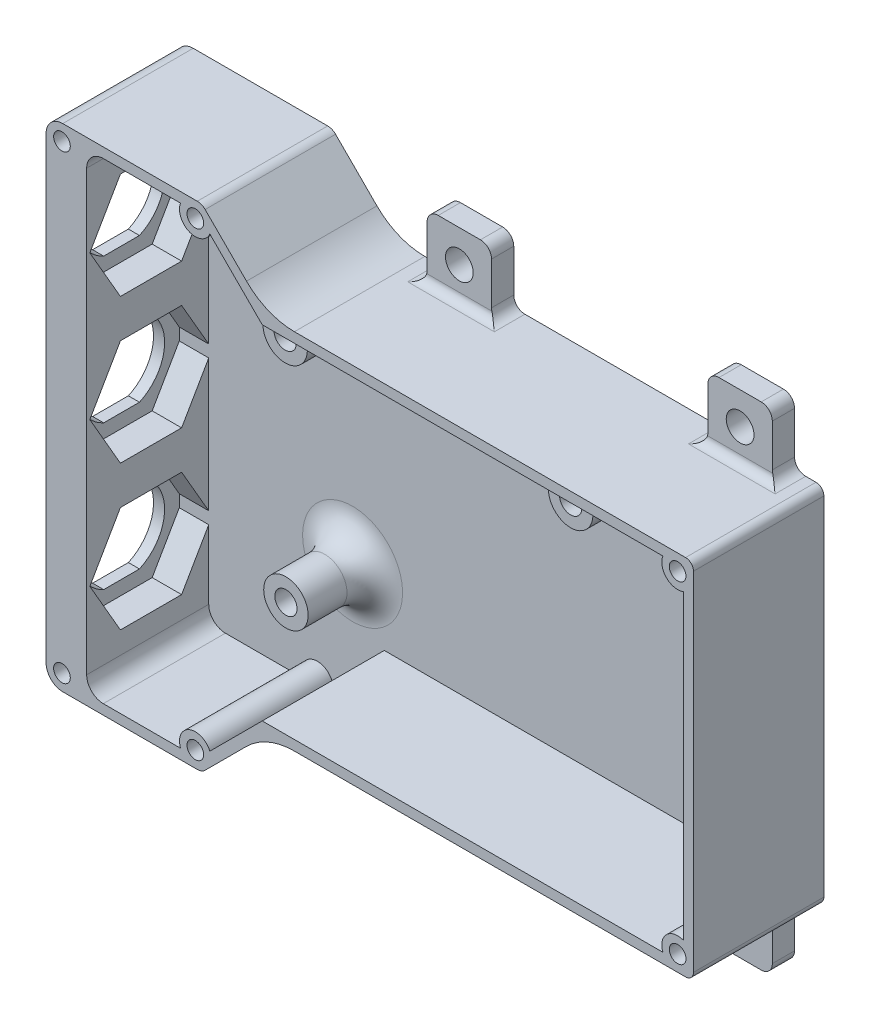
SolidWorks part; units mm, degrees
ref_plane "Front Plane" through (0, 0, 0) normal (0, 0, 1) x (1, 0, 0)
ref_plane "Top Plane" through (0, 0, 0) normal (0, 1, 0) x (1, 0, 0)
ref_plane "Right Plane" through (0, 0, 0) normal (1, 0, 0) x (0, 0, -1)
sketch "Sketch1" plane through (0, 0, 0) normal (0, 0, 1) x (1, 0, 0)
  line L0 (21.6569, -104.2696) -> (33.2669, -92.6596)
  line L1 (21.6569, -11.2696) -> (33.2619, -22.8746)
  line L2 (22.8284, -103.098) -> (34.4384, -91.488) construction
  line L3 (22.8284, -12.4412) -> (34.4334, -24.0462) construction
  line L10 (0, -100.2696) -> (20, -100.2696)
  line L11 (0, -15.2696) -> (20, -15.2696)
  line L12 (20, -100.2696) -> (31.61, -88.6596)
  line L13 (96.455, -88.6596) -> (8, -88.6596) construction
  line L14 (8, -26.8746) -> (96.455, -26.8746) construction
  line L15 (20, -15.2696) -> (31.605, -26.8746)
  line L16 (1.6569, -104.2696) -> (21.6569, -104.2696)
  line L17 (1.6569, -11.2696) -> (21.6569, -11.2696)
  line L24 (96.455, -88.6596) -> (31.61, -88.6596)
  line L26 (31.605, -26.8746) -> (96.455, -26.8746)
  line L27 (96.455, -26.8746) -> (96.455, -88.6596)
  line L28 (100.455, -92.6596) -> (33.2669, -92.6596)
  line L29 (33.2619, -22.8746) -> (100.455, -22.8746)
  line L31 (100.455, -22.8746) -> (100.455, -92.6596)
  line L33 (0, -100.2696) -> (-18.3, -100.2696)
  line L35 (0, -15.2696) -> (-18.3, -15.2696)
  line L36 (-18.3, -15.2696) -> (-18.3, -11.2696)
  line L37 (-18.3, -11.2696) -> (1.6569, -11.2696)
  line L38 (-18.3, -100.2696) -> (-18.3, -104.2696)
  line L39 (-18.3, -104.2696) -> (1.6569, -104.2696)
  line L45 (100.455, -92.6596) -> (4, -92.6596) construction
  line L46 (4, -92.6596) -> (4, -22.8746) construction
  line L47 (4, -22.8746) -> (100.455, -22.8746) construction
  line L52 (8, -88.6596) -> (8, -26.8746) construction
  dimension "D1" = 4
  dimension "D3" = 4
  dimension "D2" = 4
extrude "Boss-Extrude1" add sketch "Sketch1" along normal blind 36.78
sketch "Sketch2" plane through (0, 0, 0) normal (0, 0, -1) x (-1, 0, 0)
  line L0 (18.3, -15.2696) -> (18.3, -100.2696)
  line L16 (-33.2669, -92.6596) -> (-21.6569, -104.2696)
  line L17 (-31.61, -88.6596) -> (-96.455, -88.6596)
  line L18 (-96.455, -88.6596) -> (-96.455, -26.8746)
  line L19 (-96.455, -26.8746) -> (-31.605, -26.8746)
  line L20 (-33.2669, -92.6596) -> (-21.6569, -104.2696)
  line L21 (-20, -15.2696) -> (18.3, -15.2696)
  line L22 (18.3, -15.2696) -> (18.3, -11.2696)
  line L23 (18.3, -11.2696) -> (-21.6569, -11.2696)
  line L24 (-20, -100.2696) -> (-31.61, -88.6596)
  line L25 (-33.2619, -22.8746) -> (-100.455, -22.8746)
  line L26 (-100.455, -22.8746) -> (-100.455, -92.6596)
  line L27 (-100.455, -92.6596) -> (-33.2669, -92.6596)
  line L29 (-21.6569, -104.2696) -> (18.3, -104.2696)
  line L30 (18.3, -104.2696) -> (18.3, -100.2696)
  line L31 (18.3, -100.2696) -> (-20, -100.2696)
  line L33 (-31.605, -26.8746) -> (-20, -15.2696)
  line L35 (-21.6569, -11.2696) -> (-33.2619, -22.8746)
  line L36 (-21.6569, -11.2696) -> (-33.2619, -22.8746)
  line L38 (18.3, -15.2696) -> (18.3, -11.2696)
  line L39 (18.3, -11.2696) -> (-21.6569, -11.2696)
  line L41 (-33.2619, -22.8746) -> (-100.455, -22.8746)
  line L42 (-100.455, -22.8746) -> (-100.455, -92.6596)
  line L43 (-100.455, -92.6596) -> (-33.2669, -92.6596)
  line L45 (-21.6569, -104.2696) -> (18.3, -104.2696)
  line L46 (18.3, -104.2696) -> (18.3, -100.2696)
  dimension "D1" = 0
extrude "Boss-Extrude2" add sketch "Sketch2" against normal blind 3.5
sketch "Sketch4" plane through (-5.3, 0, 0) normal (1, 0, 0) x (0, 0, -1)
  line L0 (-13.8923, -90.5196) -> (-10.7395, -90.5196) construction
  line L1 (-13.8923, -90.5196) -> (-17.0451, -90.5196) construction
  line L2 (-13.8923, -77.0196) -> (-10.7395, -77.0196) construction
  line L3 (-13.8923, -77.0196) -> (-17.0451, -77.0196) construction
  line L4 (-13.8923, -64.5196) -> (-10.7395, -64.5196) construction
  line L5 (-13.8923, -64.5196) -> (-17.0451, -64.5196) construction
  line L6 (-13.8923, -51.0196) -> (-10.7395, -51.0196) construction
  line L7 (-13.8923, -51.0196) -> (-17.0451, -51.0196) construction
  line L8 (-13.8923, -38.5196) -> (-17.0451, -38.5196) construction
  line L9 (-13.8923, -38.5196) -> (-10.7395, -38.5196) construction
  line L10 (-13.8923, -25.0196) -> (-10.7395, -25.0196) construction
  line L11 (-13.8923, -25.0196) -> (-17.0451, -25.0196) construction
  line L12 (-13.8923, -90.5196) -> (-10.7395, -90.5196)
  line L13 (-13.8923, -90.5196) -> (-17.0451, -90.5196)
  line L14 (-13.8923, -77.0196) -> (-10.7395, -77.0196)
  line L15 (-13.8923, -77.0196) -> (-17.0451, -77.0196)
  line L16 (-13.8923, -64.5196) -> (-10.7395, -64.5196)
  line L17 (-13.8923, -64.5196) -> (-17.0451, -64.5196)
  line L18 (-13.8923, -51.0196) -> (-10.7395, -51.0196)
  line L19 (-13.8923, -51.0196) -> (-17.0451, -51.0196)
  line L20 (-13.8923, -38.5196) -> (-17.0451, -38.5196)
  line L21 (-13.8923, -38.5196) -> (-10.7395, -38.5196)
  line L22 (-13.8923, -25.0196) -> (-10.7395, -25.0196)
  line L23 (-13.8923, -25.0196) -> (-17.0451, -25.0196)
  line L24 (-13.8923, -38.8196) -> (-17.111, -38.8196)
  line L25 (-13.8923, -38.8196) -> (-10.6736, -38.8196)
  line L26 (-13.8923, -24.7196) -> (-10.6736, -24.7196)
  line L27 (-13.8923, -24.7196) -> (-17.111, -24.7196)
  line L28 (-13.8923, -64.8196) -> (-17.111, -64.8196)
  line L29 (-13.8923, -64.8196) -> (-10.6736, -64.8196)
  line L30 (-13.8923, -50.7196) -> (-10.6736, -50.7196)
  line L31 (-13.8923, -50.7196) -> (-17.111, -50.7196)
  line L32 (-13.8923, -90.8196) -> (-17.111, -90.8196)
  line L33 (-13.8923, -90.8196) -> (-10.6736, -90.8196)
  line L34 (-13.8923, -76.7196) -> (-10.6736, -76.7196)
  line L35 (-13.8923, -76.7196) -> (-17.111, -76.7196)
  line L36 (-36.78, -100.2696) -> (-3.5, -100.2696)
  line L37 (-36.78, -100.2696) -> (-3.5, -100.2696)
  line L38 (-3.5, -100.2696) -> (-3.5, -15.2696)
  line L39 (-3.5, -100.2696) -> (-3.5, -15.2696)
  line L40 (-3.5, -15.2696) -> (-36.78, -15.2696)
  line L41 (-3.5, -15.2696) -> (-36.78, -15.2696)
  line L42 (-36.78, -15.2696) -> (-36.78, -100.2696)
  arc A0 (-17.0451, -77.0196) -> (-17.0451, -90.5196) centre (-13.8923, -83.7696) ccw construction
  arc A1 (-10.7395, -90.5196) -> (-10.7395, -77.0196) centre (-13.8923, -83.7696) ccw construction
  arc A2 (-10.7395, -64.5196) -> (-10.7395, -51.0196) centre (-13.8923, -57.7696) ccw construction
  arc A3 (-17.0451, -51.0196) -> (-17.0451, -64.5196) centre (-13.8923, -57.7696) ccw construction
  arc A4 (-17.0451, -25.0196) -> (-17.0451, -38.5196) centre (-13.8923, -31.7696) ccw construction
  arc A5 (-10.7395, -38.5196) -> (-10.7395, -25.0196) centre (-13.8923, -31.7696) ccw construction
  arc A6 (-17.0451, -77.0196) -> (-17.0451, -90.5196) centre (-13.8923, -83.7696) ccw
  arc A7 (-10.7395, -90.5196) -> (-10.7395, -77.0196) centre (-13.8923, -83.7696) ccw
  arc A8 (-10.7395, -64.5196) -> (-10.7395, -51.0196) centre (-13.8923, -57.7696) ccw
  arc A9 (-17.0451, -51.0196) -> (-17.0451, -64.5196) centre (-13.8923, -57.7696) ccw
  arc A10 (-17.0451, -25.0196) -> (-17.0451, -38.5196) centre (-13.8923, -31.7696) ccw
  arc A11 (-10.7395, -38.5196) -> (-10.7395, -25.0196) centre (-13.8923, -31.7696) ccw
  arc A12 (-17.111, -24.7196) -> (-17.111, -38.8196) centre (-13.8923, -31.7696) ccw
  arc A13 (-10.6736, -38.8196) -> (-10.6736, -24.7196) centre (-13.8923, -31.7696) ccw
  arc A14 (-17.111, -50.7196) -> (-17.111, -64.8196) centre (-13.8923, -57.7696) ccw
  arc A15 (-10.6736, -64.8196) -> (-10.6736, -50.7196) centre (-13.8923, -57.7696) ccw
  arc A16 (-17.111, -76.7196) -> (-17.111, -90.8196) centre (-13.8923, -83.7696) ccw
  arc A17 (-10.6736, -90.8196) -> (-10.6736, -76.7196) centre (-13.8923, -83.7696) ccw
  line M1 (-21.5451, -64.5196) -> (-18.3923, -64.5196)
  arc M2 (-18.3923, -64.5196) -> (-18.3923, -51.0196) centre (-18.3923, -57.7696) cw
  line M3 (-18.3923, -51.0196) -> (-21.5451, -51.0196)
  arc M4 (-21.5451, -51.0196) -> (-21.5451, -64.5196) centre (-18.3923, -57.7696) ccw
  dimension "D1" = 0.3
extrude "Boss-Extrude3" add sketch "Sketch4" against normal blind 2 contours L41 L42 L37 L39 A17 L33 L32 A16 L35 L34 A15 L29 L28 A14 L31 L30 A13 L25 L24 A12 L27 L26 M1 M4 M3 M2 | M4 M1 M2 M3 region at (-5.3, -57.7696, 35.8672) region at (-5.3, -57.7696, 25.6881)
sketch "Sketch5" plane through (-5.3, 0, 0) normal (1, 0, 0) x (0, 0, -1)
  line L18 (-13.8923, -24.7196) -> (-13.8923, -38.8196)
  line L19 (-10.6736, -24.7196) -> (-17.111, -24.7196) construction
  line L20 (-17.111, -38.8196) -> (-10.6736, -38.8196) construction
  line L21 (-13.8923, -50.7196) -> (-13.8923, -64.8196)
  line L22 (-10.6736, -50.7196) -> (-17.111, -50.7196) construction
  line L23 (-17.111, -64.8196) -> (-10.6736, -64.8196) construction
  line L24 (-13.8923, -76.7196) -> (-13.8923, -90.8196)
  line L25 (-10.6736, -76.7196) -> (-17.111, -76.7196) construction
  line L26 (-17.111, -90.8196) -> (-10.6736, -90.8196) construction
  line L27 (-24.9116, -83.7696) -> (-19.402, -93.3126)
  line L28 (-24.7384, -31.7696) -> (-19.3154, -41.1626)
  line L29 (-19.3154, -41.1626) -> (-8.4692, -41.1626)
  line L30 (-8.4692, -41.1626) -> (-3.0462, -31.7696)
  line L31 (-3.0462, -31.7696) -> (-8.4692, -22.3766)
  line L32 (-8.4692, -22.3766) -> (-19.3154, -22.3766)
  line L33 (-19.3154, -22.3766) -> (-24.7384, -31.7696)
  line L34 (-24.7384, -57.7696) -> (-19.3154, -67.1626)
  line L35 (-19.3154, -67.1626) -> (-8.4692, -67.1626)
  line L36 (-36.78, -100.2696) -> (-3.5, -100.2696) construction
  line L37 (-36.78, -15.2696) -> (-36.78, -100.2696) construction
  line L38 (-3.5, -15.2696) -> (-36.78, -15.2696) construction
  line L39 (-3.5, -100.2696) -> (-3.5, -15.2696) construction
  line L40 (-36.78, -100.2696) -> (-3.5, -100.2696)
  line L41 (-36.78, -15.2696) -> (-36.78, -100.2696)
  line L42 (-3.5, -15.2696) -> (-36.78, -15.2696)
  line L43 (-3.5, -100.2696) -> (-3.5, -15.2696)
  line L44 (-8.4692, -67.1626) -> (-3.0462, -57.7696)
  line L45 (-3.0462, -57.7696) -> (-8.4692, -48.3766)
  line L46 (-8.4692, -48.3766) -> (-19.3154, -48.3766)
  line L47 (-19.3154, -48.3766) -> (-24.7384, -57.7696)
  line L48 (-24.7384, -83.7696) -> (-19.3154, -93.1626)
  line L49 (-19.3154, -93.1626) -> (-8.4692, -93.1626)
  line L50 (-8.4692, -93.1626) -> (-3.0462, -83.7696)
  line L51 (-3.0462, -83.7696) -> (-8.4692, -74.3766)
  line L52 (-8.4692, -74.3766) -> (-19.3154, -74.3766)
  line L53 (-19.3154, -74.3766) -> (-24.7384, -83.7696)
  line L54 (-19.402, -93.3126) -> (-8.3826, -93.3126)
  line L55 (-8.3826, -93.3126) -> (-2.873, -83.7696)
  line L56 (-2.873, -83.7696) -> (-8.3826, -74.2266)
  line L57 (-8.3826, -74.2266) -> (-19.402, -74.2266)
  line L58 (-19.402, -74.2266) -> (-24.9116, -83.7696)
  line L59 (-19.402, -22.2266) -> (-24.9116, -31.7696)
  line L60 (-24.9116, -31.7696) -> (-19.402, -41.3126)
  line L61 (-19.402, -41.3126) -> (-8.3826, -41.3126)
  line L62 (-8.3826, -41.3126) -> (-2.873, -31.7696)
  line L63 (-2.873, -31.7696) -> (-8.3826, -22.2266)
  line L64 (-8.3826, -22.2266) -> (-19.402, -22.2266)
  line L65 (-19.402, -48.2266) -> (-24.9116, -57.7696)
  line L66 (-24.9116, -57.7696) -> (-19.402, -67.3126)
  line L67 (-19.402, -67.3126) -> (-8.3826, -67.3126)
  line L68 (-8.3826, -67.3126) -> (-2.873, -57.7696)
  line L69 (-2.873, -57.7696) -> (-8.3826, -48.2266)
  line L70 (-8.3826, -48.2266) -> (-19.402, -48.2266)
  circle A0 centre (-13.8923, -31.7696) radius 9.393 construction
  circle A1 centre (-13.8923, -57.7696) radius 9.393 construction
  circle A2 centre (-13.8923, -83.7696) radius 9.393 construction
  line M16 (-3.5, -15.2696) -> (-36.78, -15.2696)
  line M17 (-36.78, -15.2696) -> (-36.78, -100.2696)
  line M18 (-36.78, -100.2696) -> (-3.5, -100.2696)
  line M19 (-3.5, -100.2696) -> (-3.5, -15.2696)
  dimension "D1" = 0.15
extrude "Boss-Extrude4" add sketch "Sketch5" along normal up to surface (5.3 mm away) contours L46 L45 L44 L34 L32 L30 L29 L28 M19 M16 M17 M18 region at (-5.3, -88.9975, 22.9473)
sketch "Sketch6" plane through (0, 0, 36.78) normal (0, 0, 1) x (1, 0, 0)
  line L1 (-48.9743, 0) -> (133.8378, 0)
  line L2 (-48.9743, 0) -> (-48.9743, -122.4446)
  line L3 (-48.9743, -122.4446) -> (133.8378, -122.4446)
  line L4 (133.8378, 0) -> (133.8378, -122.4446)
extrude "Cut-Extrude1" cut sketch "Sketch6" against normal blind 4
ref_plane "Plane1" through (5, 0, 0) normal (1, 0, 0) x (0, 0, -1)
fillet "Fillet4" radius 10 2 edges at (33.2669, -92.6596, 16.39) (33.2619, -22.8746, 16.39)
sketch "Sketch8" plane through (0, 0, 32.78) normal (0, 0, 1) x (1, 0, 0)
  line L0 (100.455, -92.6596) -> (100.455, -22.8746) construction
  line L3 (100.455, -88.6596) -> (100.455, -26.8746)
  line L6 (96.455, -26.8746) -> (96.455, -88.6596)
  line L7 (96.455, -26.8746) -> (100.455, -26.8746)
  line L8 (96.455, -88.6596) -> (100.455, -88.6596)
extrude "Cut-Extrude2" cut sketch "Sketch8" against normal up to surface (29.28 mm away) up to face at (13.2163, -57.7691, 3.5)
sketch "Sketch9" plane through (100.455, 0, 0) normal (1, 0, 0) x (0, 0, -1)
  line L0 (-32.78, -92.6596) -> (-32.78, -88.6596) construction
  line L1 (-3.5, -88.6596) -> (-32.78, -88.6596) construction
  line L2 (-32.78, -92.6596) -> (0, -92.6596) construction
  line L3 (0, -92.6596) -> (0, -22.8746) construction
  line L4 (-3.5, -88.6596) -> (-3.5, -26.8746) construction
  line L5 (-3.5, -26.8746) -> (-32.78, -26.8746) construction
  line L6 (-32.78, -26.8746) -> (-32.78, -22.8746) construction
  line L7 (-32.78, -22.8746) -> (0, -22.8746) construction
  line L8 (-32.78, -92.6596) -> (-32.78, -88.6596)
  line L9 (-3.5, -88.6596) -> (-32.78, -88.6596)
  line L10 (-32.78, -92.6596) -> (0, -92.6596)
  line L11 (0, -92.6596) -> (0, -22.8746)
  line L12 (-3.5, -88.6596) -> (-3.5, -26.8746)
  line L13 (-3.5, -26.8746) -> (-32.78, -26.8746)
  line L14 (-32.78, -26.8746) -> (-32.78, -22.8746)
  line L15 (-32.78, -22.8746) -> (0, -22.8746)
extrude "Boss-Extrude6" add sketch "Sketch9" along normal blind 11
sketch "Sketch10" plane through (0, 0, 32.78) normal (0, 0, 1) x (1, 0, 0)
  line L0 (111.455, -88.6596) -> (31.61, -88.6596) construction
  line L2 (31.605, -26.8746) -> (111.455, -26.8746) construction
  line L4 (111.455, -88.6596) -> (107.455, -88.6596)
  line L6 (107.455, -26.8746) -> (111.455, -26.8746)
  line L8 (111.455, -26.8746) -> (107.455, -26.8746)
  line L9 (107.455, -26.8746) -> (107.455, -88.6596)
  line L10 (111.455, -26.8746) -> (111.455, -88.6596)
  line M1 (31.605, -26.8746) -> (111.455, -26.8746)
  line M19 (111.455, -88.6596) -> (31.61, -88.6596)
extrude "Boss-Extrude7" add sketch "Sketch10" against normal up to surface (29.28 mm away) contours L10 L9 M1 M19 region at (109.455, -57.7671, 32.78) up to face at (-12.8, -57.7696, 3.5)
sketch "Sketch24" plane through (0, 0, 32.78) normal (0, 0, 1) x (1, 0, 0)
  line L2 (111.455, -22.8746) -> (37.404, -22.8746) construction
  line L3 (111.455, -22.8746) -> (111.455, -92.6596) construction
  line L4 (31.605, -26.8746) -> (107.455, -26.8746) construction
  line L5 (107.455, -26.8746) -> (107.455, -88.6596) construction
  line L6 (111.455, -22.8746) -> (37.404, -22.8746)
  line L7 (111.455, -22.8746) -> (111.455, -92.6596)
  line L8 (31.605, -26.8746) -> (107.455, -26.8746)
  line L9 (107.455, -26.8746) -> (107.455, -88.6596)
  line L10 (107.455, -26.8746) -> (107.455, -29.8746)
  line L11 (107.455, -26.8746) -> (104.455, -26.8746)
  line L12 (104.455, -26.8746) -> (107.455, -29.8746)
  line L13 (107.455, -88.6596) -> (104.455, -88.6596)
  line L14 (107.455, -88.6596) -> (31.61, -88.6596) construction
  line L15 (104.455, -88.6596) -> (107.455, -85.6596)
  line M1 (107.455, -26.8746) -> (107.455, -88.6596)
  line M2 (107.455, -88.6596) -> (31.61, -88.6596)
extrude "Boss-Extrude10" add sketch "Sketch24" against normal up to surface (29.28 mm away) contours L15 M2 M1 | L8 L12 M1 region at (106.455, -87.6596, 32.78) region at (106.455, -27.8746, 32.78) up to face at (-12.8, -57.7696, 3.5)
sketch "Sketch28" plane through (0, 0, 32.78) normal (0, 0, 1) x (1, 0, 0)
  line L1 (-7.3, -83.7696) -> (-7.3, -31.7696)
  line L2 (-7.3, -31.7696) -> (-7.3, -6.2489)
  line L3 (-7.3, -6.2489) -> (-26.3455, -6.2489)
  line L4 (-26.3455, -6.2489) -> (-26.3455, -107.7031)
  line L5 (-26.3455, -107.7031) -> (-7.3, -107.7031)
  line L6 (-7.3, -107.7031) -> (-7.3, -83.7696)
extrude "Cut-Extrude12" cut sketch "Sketch28" against normal through all
sketch "Sketch29" plane through (0, 0, 32.78) normal (0, 0, 1) x (1, 0, 0)
  line L0 (-7.3, -104.2696) -> (21.6569, -104.2696) construction
  line L1 (21.6569, -104.2696) -> (30.3379, -95.5885) construction
  line L2 (37.409, -92.6596) -> (111.455, -92.6596) construction
  line L3 (111.455, -22.8746) -> (111.455, -92.6596) construction
  line L4 (111.455, -22.8746) -> (37.404, -22.8746) construction
  line L5 (30.3329, -19.9457) -> (21.6569, -11.2696) construction
  line L6 (21.6569, -11.2696) -> (-7.3, -11.2696) construction
  line L7 (-7.3, -104.2696) -> (21.6569, -104.2696)
  line L8 (21.6569, -104.2696) -> (30.3379, -95.5885)
  line L9 (37.409, -92.6596) -> (111.455, -92.6596)
  line L10 (111.455, -22.8746) -> (111.455, -92.6596)
  line L11 (111.455, -22.8746) -> (37.404, -22.8746)
  line L12 (30.3329, -19.9457) -> (21.6569, -11.2696)
  line L13 (21.6569, -11.2696) -> (-7.3, -11.2696)
  line L14 (-7.3, -102.0736) -> (20.7472, -102.0736)
  line L15 (20.7472, -102.0736) -> (28.7851, -94.0357)
  line L16 (37.409, -90.4636) -> (109.259, -90.4636)
  line L17 (109.259, -25.0706) -> (109.259, -90.4636)
  line L18 (109.259, -25.0706) -> (37.404, -25.0706)
  line L19 (28.7801, -21.4985) -> (20.7472, -13.4656)
  line L20 (20.7472, -13.4656) -> (-7.3, -13.4656)
  line L21 (-7.3, -13.4656) -> (-7.3, -11.2696)
  line L22 (-7.3, -102.0736) -> (-7.3, -104.2696)
  arc A0 (37.409, -92.6596) -> (30.3379, -95.5885) centre (37.409, -102.6596) ccw construction
  arc A1 (30.3329, -19.9457) -> (37.404, -22.8746) centre (37.404, -12.8746) ccw construction
  arc A2 (37.409, -92.6596) -> (30.3379, -95.5885) centre (37.409, -102.6596) ccw
  arc A3 (30.3329, -19.9457) -> (37.404, -22.8746) centre (37.404, -12.8746) ccw
  arc A4 (37.409, -90.4636) -> (28.7851, -94.0357) centre (37.409, -102.6596) ccw
  arc A5 (28.7801, -21.4985) -> (37.404, -25.0706) centre (37.404, -12.8746) ccw
  dimension "D1" = 2.196
extrude "Cut-Extrude13" cut sketch "Sketch29" against normal through all
sketch "Sketch30" plane through (0, 0, 0) normal (0, 0, -1) x (-1, 0, 0)
  line L0 (-37.404, -25.0706) -> (-109.259, -25.0706) construction
  line L1 (-109.259, -25.0706) -> (-109.259, -90.4636) construction
  line L2 (-109.259, -90.4636) -> (-37.409, -90.4636) construction
  line L3 (-28.7851, -94.0357) -> (-20.7472, -102.0736) construction
  line L4 (-20.7472, -102.0736) -> (7.3, -102.0736) construction
  line L5 (7.3, -102.0736) -> (7.3, -13.4656) construction
  line L6 (7.3, -13.4656) -> (-20.7472, -13.4656) construction
  line L7 (-20.7472, -13.4656) -> (-28.7801, -21.4985) construction
  line L8 (-109.259, -25.0706) -> (-109.259, -90.4636)
  line L9 (-109.259, -90.4636) -> (-37.409, -90.4636)
  line L10 (-28.7851, -94.0357) -> (-20.7472, -102.0736)
  line L11 (-20.7472, -102.0736) -> (7.3, -102.0736)
  line L12 (7.3, -102.0736) -> (7.3, -13.4656)
  line L13 (7.3, -13.4656) -> (-20.7472, -13.4656)
  line L14 (-20.7472, -13.4656) -> (-28.7801, -21.4985)
  line L15 (-37.404, -25.0706) -> (-109.259, -25.0706)
  arc A0 (-28.7851, -94.0357) -> (-37.409, -90.4636) centre (-37.409, -102.6596) ccw construction
  arc A1 (-37.404, -25.0706) -> (-28.7801, -21.4985) centre (-37.404, -12.8746) ccw construction
  arc A2 (-28.7851, -94.0357) -> (-37.409, -90.4636) centre (-37.409, -102.6596) ccw
  arc A3 (-37.404, -25.0706) -> (-28.7801, -21.4985) centre (-37.404, -12.8746) ccw
extrude "Cut-Extrude14" cut sketch "Sketch30" against normal blind 2
fillet "Fillet26" radius 3 2 edges at (-7.3, -13.4656, 17.39) (-7.3, -102.0736, 17.39)
fillet "Fillet27" radius 3 2 edges at (0, -100.2696, 18.14) (0, -15.2696, 18.14)
fillet "Fillet28" radius 2 4 edges at (20, -15.2696, 18.14) (20.7472, -13.4656, 17.39) (20, -100.2696, 18.14) (20.7472, -102.0736, 17.39) tangent propagation no
sketch "Sketch33" plane through (0, 0, 32.78) normal (0, 0, 1) x (1, 0, 0)
  line L2 (109.259, -25.0706) -> (109.259, -90.4636) construction
  line L3 (109.259, -90.4636) -> (37.409, -90.4636) construction
  line L4 (19.9188, -102.0736) -> (-4.3, -102.0736) construction
  line L5 (28.7851, -94.0357) -> (21.333, -101.4878) construction
  line L6 (-4.3, -13.4656) -> (19.9188, -13.4656) construction
  line L7 (21.333, -14.0514) -> (28.7801, -21.4985) construction
  line L8 (-7.3, -99.0736) -> (-7.3, -16.4656) construction
  line L9 (37.404, -25.0706) -> (109.259, -25.0706) construction
  circle A0 centre (106.406, -27.9236) radius 1.5
  circle A1 centre (106.406, -27.9236) radius 2.853
  circle A2 centre (106.406, -87.6106) radius 2.853
  circle A3 centre (19.5655, -99.2206) radius 2.853
  circle A4 centre (19.5655, -16.3186) radius 2.853
  circle A5 centre (-4.447, -16.3186) radius 2.853
  circle A6 centre (-4.447, -99.2206) radius 2.853
  dimension "D3" = 3
  dimension "D4" = 5.706
  dimension "D2" = 2.853
extrude "Boss-Extrude13" add sketch "Sketch33" against normal up to surface (29.28 mm away) contours A4 | A3 | A2 | A1 up to face at (20.7548, -57.769, 3.5)
sketch "Sketch34" plane through (0, 0, 32.78) normal (0, 0, 1) x (1, 0, 0)
  circle A0 centre (106.406, -27.9236) radius 2.853 construction
  circle A1 centre (106.406, -87.6106) radius 2.853 construction
  circle A2 centre (19.5655, -99.2206) radius 2.853 construction
  circle A3 centre (-4.447, -99.2206) radius 2.853 construction
  circle A4 centre (19.5655, -16.3186) radius 2.853 construction
  circle A5 centre (-4.447, -16.3186) radius 2.853 construction
  circle A6 centre (106.406, -27.9236) radius 2.853
  circle A7 centre (106.406, -87.6106) radius 2.853
  circle A8 centre (19.5655, -99.2206) radius 2.853
  circle A9 centre (-4.447, -99.2206) radius 2.853
  circle A10 centre (19.5655, -16.3186) radius 2.853
  circle A11 centre (-4.447, -16.3186) radius 2.853
  circle A12 centre (-4.447, -16.3186) radius 1.5
  circle A13 centre (19.5655, -16.3186) radius 1.5
  circle A14 centre (106.406, -27.9236) radius 1.5
  circle A15 centre (106.406, -87.6106) radius 1.5
  circle A16 centre (19.5655, -99.2206) radius 1.5
  circle A17 centre (-4.447, -99.2206) radius 1.5
extrude "Cut-Extrude15" cut sketch "Sketch34" against normal blind 20 contours A12 | A13 | A14 | A15 | A16 | A17
fillet "Fillet29" radius 1.425 2 edges at (109.259, -25.0706, 17.39) (109.259, -90.4636, 17.39)
ref_plane "Plane2" through (0, 0, 20.78) normal (0, 0, 1) x (1, 0, 0)
sketch "Sketch35" plane through (0, 0, 20.78) normal (0, 0, 1) x (1, 0, 0)
  line L0 (31.61, -88.6596) -> (103.7528, -88.6596) construction
  line L1 (107.455, -30.5767) -> (107.455, -84.9574) construction
  line L2 (103.7528, -26.8746) -> (31.605, -26.8746) construction
  line L3 (31.61, -88.6596) -> (103.7528, -88.6596)
  line L4 (107.455, -30.5767) -> (107.455, -84.9574)
  line L5 (103.7528, -26.8746) -> (31.605, -26.8746)
  line L6 (107.455, -84.9574) -> (107.455, -88.6596)
  line L7 (107.455, -88.6596) -> (103.7528, -88.6596)
  line L8 (103.7528, -26.8746) -> (107.455, -26.8746)
  line L9 (107.455, -26.8746) -> (107.455, -30.5767)
  line L10 (31.605, -26.8746) -> (31.61, -88.6596)
extrude "Cut-Extrude16" cut sketch "Sketch35" against normal up to surface (17.28 mm away) up to face at (20.4692, -57.769, 3.5)
sketch "Sketch36" plane through (0, 0, 32.78) normal (0, 0, 1) x (1, 0, 0)
  line L1 (-22.7026, -2.6518) -> (121.9699, -2.6518)
  line L2 (-22.7026, -2.6518) -> (-22.7026, -112.3259)
  line L3 (-22.7026, -112.3259) -> (121.9699, -112.3259)
  line L4 (121.9699, -2.6518) -> (121.9699, -112.3259)
extrude "Cut-Extrude17" cut sketch "Sketch36" against normal blind 7.3
sketch "Sketch38" plane through (0, 0, 3.5) normal (0, 0, 1) x (1, 0, 0)
  circle A2 centre (25.7592, -36.7486) radius 2
  circle A4 centre (77.1688, -36.7486) radius 2
  circle A6 centre (25.8989, -78.0236) radius 2
  circle A7 centre (102.7085, -78.0236) radius 4
  circle A8 centre (102.7085, -78.0236) radius 2
  circle A9 centre (77.1688, -36.7486) radius 4
  circle A10 centre (25.7592, -36.7486) radius 4
  circle A11 centre (25.8989, -78.0236) radius 4
  dimension "D1" = 2
extrude "Boss-Extrude14" add sketch "Sketch38" along normal up to surface (12 mm away) contours A7 A8 | A11 A6 | A10 A2 | A9 A4 region at (98.8216, -78.0236, 3.5) region at (73.2819, -36.7486, 3.5) region at (21.8723, -36.7486, 3.5) region at (22.012, -78.0236, 3.5)
fillet "Fillet30" radius 5 4 edges at (98.7085, -78.0236, 3.5) (73.1688, -36.7486, 3.5) (21.7592, -36.7486, 3.5) (21.8989, -78.0236, 3.5)
sketch "Sketch39" plane through (0, 0, 2) normal (0, 0, -1) x (-1, 0, 0)
  line L0 (-107.834, -90.4636) -> (-37.409, -90.4636) construction
  line L1 (-37.404, -25.0706) -> (-107.834, -25.0706) construction
  line L2 (-107.834, -90.4636) -> (-37.409, -90.4636)
  line L3 (-37.404, -25.0706) -> (-107.834, -25.0706)
  line L4 (-103.9747, -25.0706) -> (-103.9747, -13.4706)
  line L5 (-103.9747, -13.4706) -> (-92.3747, -13.4706)
  line L6 (-92.3747, -13.4706) -> (-92.3747, -25.0706)
  line L7 (-53.4219, -25.0706) -> (-53.4219, -13.4706)
  line L8 (-53.4219, -13.4706) -> (-41.8219, -13.4706)
  line L9 (-41.8219, -13.4706) -> (-41.8219, -25.0706)
  line L10 (-109.259, -57.7671) -> (-21.9967, -57.7671)
  line L11 (-109.259, -26.4956) -> (-109.259, -89.0386) construction
  line L12 (-37.404, -90.4636) -> (-107.834, -90.4636)
  line L13 (-41.8219, -102.0636) -> (-41.8219, -90.4636)
  line L14 (-53.4219, -102.0636) -> (-41.8219, -102.0636)
  line L15 (-53.4219, -90.4636) -> (-53.4219, -102.0636)
  line L16 (-103.9747, -90.4636) -> (-103.9747, -102.0636)
  line L17 (-103.9747, -102.0636) -> (-92.3747, -102.0636)
  line L18 (-92.3747, -102.0636) -> (-92.3747, -90.4636)
  line L19 (4.3, -13.4656) -> (-19.9188, -13.4656) construction
  line L20 (-19.9188, -102.0736) -> (4.3, -102.0736) construction
  line L21 (4.3, -13.4656) -> (-19.9188, -13.4656)
  line L22 (-19.9188, -102.0736) -> (4.3, -102.0736)
  circle A0 centre (-98.1747, -19.2706) radius 2.5
  circle A1 centre (-47.6219, -19.2706) radius 2.5
  circle A2 centre (-47.6219, -96.2636) radius 2.5
  circle A3 centre (-98.1747, -96.2636) radius 2.5
  point P37 (0, 0)
  point P38 (0, 0)
  point P39 (-103.9747, -96.2636)
  point P40 (-99.8994, -95.4636)
  point P41 (-98.1747, -102.0636)
  point P42 (-53.4219, -96.2636)
  point P43 (-47.6219, -102.0636)
  dimension "D1" = 11.6
  dimension "D2" = 11.6
  dimension "D3" = 11.6
  dimension "D4" = 11.6
extrude "Boss-Extrude15" add sketch "Sketch39" against normal blind 4 contours L9 L8 L7 L3 A1 | L6 L5 L4 L3 A0 | L17 L18 L12 L16 A3 | L12 L15 L14 L13 A2 region at (47.6219, -90.6276, 2) region at (98.1747, -90.6276, 2) region at (98.1747, -24.9066, 2) region at (47.6219, -24.9066, 2)
fillet "Fillet31" radius 2 16 edges at (53.4219, -102.0636, 4) (53.4219, -90.4636, 4) (41.8219, -90.4636, 4) (41.8219, -102.0636, 4) (92.3747, -90.4636, 4) (92.3747, -102.0636, 4) (103.9747, -102.0636, 4) (103.9747, -90.4636, 4) (103.9747, -25.0706, 4) (103.9747, -13.4706, 4) (92.3747, -13.4706, 4) (92.3747, -25.0706, 4) (41.8219, -25.0706, 4) (53.4219, -25.0706, 4) (41.8219, -13.4706, 4) (53.4219, -13.4706, 4)
fillet "Fillet32" radius 1.5 4 edges at (47.6219, -25.0706, 6) (98.1747, -25.0706, 6) (98.1747, -90.4636, 6) (47.6219, -90.4636, 6)
